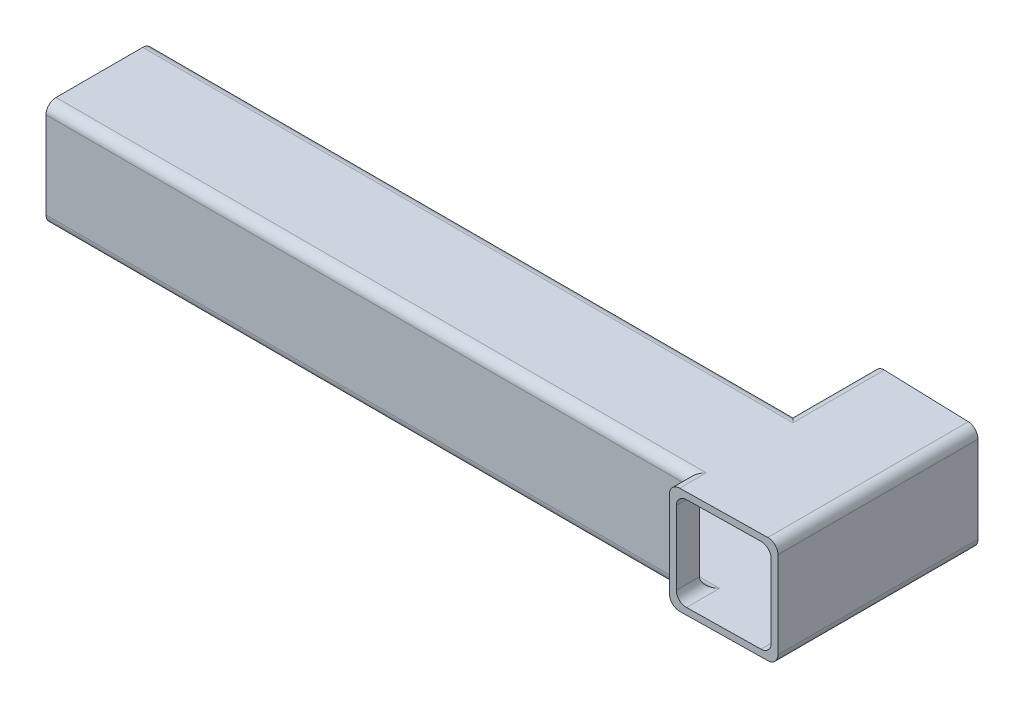
SolidWorks part; units mm, degrees
ref_plane "Front Plane" through (0, 0, 0) normal (0, 0, 1) x (1, 0, 0)
ref_plane "Top Plane" through (0, 0, 0) normal (0, 1, 0) x (1, 0, 0)
ref_plane "Right Plane" through (0, 0, 0) normal (1, 0, 0) x (0, 0, -1)
sketch "Sketch1" plane through (0, 0, 0) normal (1, 0, 0) x (0, 0, -1)
  line L0 (3.175, 22.225) -> (47.625, 22.225)
  line L1 (0, -25.4) -> (50.8, -25.4)
  line L2 (0, -25.4) -> (0, 25.4)
  line L3 (0, 25.4) -> (50.8, 25.4)
  line L4 (50.8, -25.4) -> (50.8, 25.4)
  line L5 (0, -25.4) -> (50.8, 25.4) construction
  line L6 (0, 25.4) -> (50.8, -25.4) construction
  line L7 (47.625, -22.225) -> (47.625, 22.225)
  line L8 (3.175, -22.225) -> (47.625, -22.225)
  line L9 (3.175, -22.225) -> (3.175, 22.225)
  line L10 (0, -31.4743) -> (0, 34.7184) construction
  line L11 (-8.1938, 0) -> (66.3216, 0) construction
  point P0 (25.4, 0)
  point P15 (0, 0)
  point P16 (0, -31.4743)
  dimension "D1" = 50.8
  dimension "D2" = 50.8
  dimension "D3" = 3.175
extrude "Boss-Extrude1" add sketch "Sketch1" along normal blind 304.8 contours L1 L4 L3 L2 L8 L9 L0 L7 region at (0, 0, -0.7184)
sketch "Sketch2" plane through (0, 0, 0) normal (0, 0, 1) x (1, 0, 0)
  line L0 (-9.0901, 0) -> (390.0692, 0) construction
  line L1 (307.9623, 22.225) -> (352.4377, 22.225)
  line L2 (304.7873, -25.4) -> (355.6127, -25.4)
  line L3 (304.7873, -25.4) -> (304.7873, 25.4)
  line L4 (304.7873, 25.4) -> (355.6127, 25.4)
  line L5 (355.6127, -25.4) -> (355.6127, 25.4)
  line L6 (304.7873, -25.4) -> (355.6127, 25.4) construction
  line L7 (304.7873, 25.4) -> (355.6127, -25.4) construction
  line L8 (352.4377, -22.225) -> (352.4377, 22.225)
  line L9 (307.9623, -22.225) -> (352.4377, -22.225)
  line L10 (307.9623, -22.225) -> (307.9623, 22.225)
  point P4 (330.2, 0)
  dimension "D1" = 50.8254
  dimension "D2" = 330.2
  dimension "D3" = 50.8
  dimension "D4" = 3.175
extrude "Boss-Extrude2" add sketch "Sketch2" along normal blind 7.9375 and the other way blind 89.6938 contours L2 L5 L4 L3 L9 L10 L1 L8 region at (305.5059, 0, 0)
sketch "Sketch3" plane through (0, 25.4, 0) normal (0, 1, 0) x (1, 0, 0)
  line L0 (304.7873, 89.6938) -> (355.6127, 88.1063)
  line L1 (304.7873, 89.6938) -> (355.6127, 89.6938) construction
  line L2 (355.6127, 89.6938) -> (355.6127, -7.9375) construction
  line L3 (355.6127, 88.1063) -> (355.6127, 89.6938)
  line L4 (355.6127, 89.6938) -> (304.7873, 89.6938)
  line L5 (304.7873, -7.9375) -> (355.6127, -7.1437)
  line L6 (355.6127, -7.1437) -> (355.6127, -7.9375)
  line L7 (355.6127, -7.9375) -> (304.7873, -7.9375)
  dimension "D1" = 0.7937
  dimension "D2" = 95.25
extrude "Cut-Extrude1" cut sketch "Sketch3" against normal through all
fillet "Fillet1" radius 4.7625 10 edges at (152.3936, -25.4, 0) (152.3936, -25.4, -50.8) (152.3936, 25.4, -50.8) (152.3936, 25.4, 0) (304.7873, 25.4, -70.2469) (355.6127, 25.4, -40.4812) (355.6127, -25.4, -40.4812) (304.7873, -25.4, -70.2469) (304.7873, 25.4, 3.9688) (304.7873, -25.4, 3.9688)
ref_plane "Plane1" through (0, -22.225, -47.625) normal (0, 1, 0) x (1, 0, 0)
extrude "Cut-Extrude2" cut sketch "Sketch1<3>" along normal up to next contours L9 L8 L7 L0 region at (0, 0, -25.4)
sketch "Sketch1<3>" plane through (0, 0, 0) normal (1, 0, 0) x (0, 0, -1) same geometry as "Sketch1"
fillet "Fillet3" radius 4.7625 10 edges at (352.4377, -22.225, -40.506) (352.4377, 22.225, -40.506) (307.9623, 22.225, -68.6098) (307.9623, 22.225, 2.3565) (307.9623, -22.225, 2.3565) (307.9623, -22.225, -68.6098) (153.9811, -22.225, -3.175) (153.9811, -22.225, -47.625) (153.9811, 22.225, -47.625) (153.9811, 22.225, -3.175)
